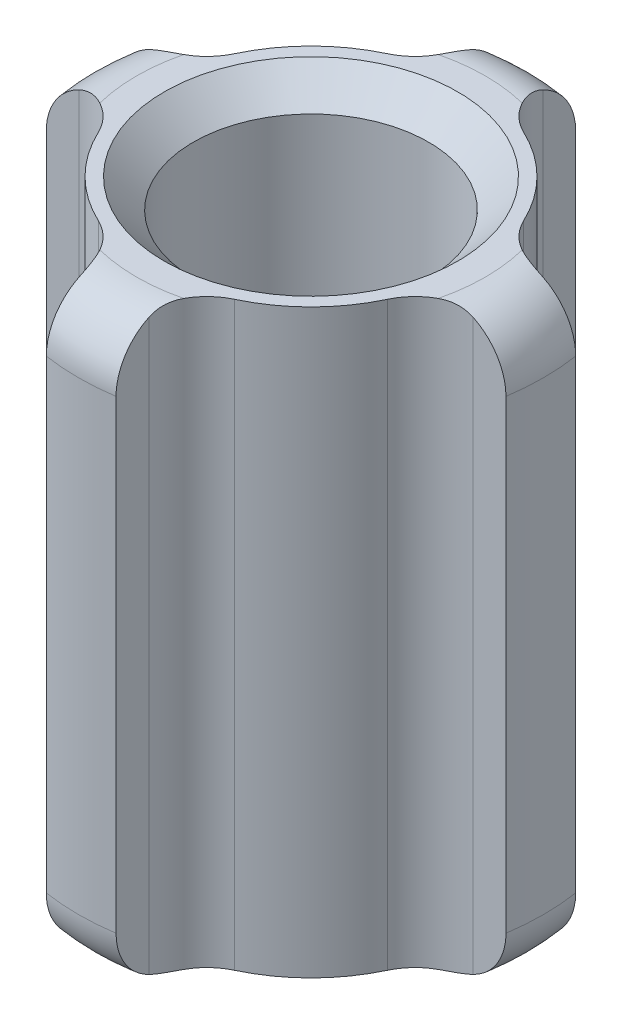
SolidWorks part; units mm, degrees
material "ABS"
ref_plane "Front Plane" through (0, 0, 0) normal (0, 0, 1) x (1, 0, 0)
ref_plane "Top Plane" through (0, 0, 0) normal (0, 1, 0) x (1, 0, 0)
ref_plane "Right Plane" through (0, 0, 0) normal (1, 0, 0) x (0, 0, -1)
sketch "Sketch1" plane through (0, 0, 0) normal (0, 1, 0) x (1, 0, 0)
  line L0 (-0.6, -3.9547) -> (-0.6, -2.6837)
  line L1 (0.6, -3.9547) -> (0.6, -2.6837)
  line L2 (-0.6, 2.6837) -> (-0.6, 3.9547)
  line L3 (0.6, 2.6837) -> (0.6, 3.9547)
  line L4 (-3.9547, 0.6) -> (-2.6837, 0.6)
  line L5 (-3.9547, -0.6) -> (-2.6837, -0.6)
  line L6 (2.6837, -0.6) -> (3.9547, -0.6)
  line L7 (2.6837, 0.6) -> (3.9547, 0.6)
  circle A0 centre (0, 0) radius 2.025
  arc A1 (-0.6, -3.9547) -> (0.6, -3.9547) centre (0, 0) ccw
  arc A2 (-0.6, 2.6837) -> (-2.6837, 0.6) centre (0, 0) ccw
  arc A3 (-3.9547, 0.6) -> (-3.9547, -0.6) centre (0, 0) ccw
  arc A4 (0.6, 3.9547) -> (-0.6, 3.9547) centre (0, 0) ccw
  arc A5 (3.9547, -0.6) -> (3.9547, 0.6) centre (0, 0) ccw
  arc A6 (-2.6837, -0.6) -> (-0.6, -2.6837) centre (0, 0) ccw
  arc A7 (0.6, -2.6837) -> (2.6837, -0.6) centre (0, 0) ccw
  arc A8 (2.6837, 0.6) -> (0.6, 2.6837) centre (0, 0) ccw
  dimension "D1" = 4.05
  dimension "D2" = 8
  dimension "D5" = 5.5
  dimension "D3" = 1.2
  dimension "D4" = 1.2
extrude "Boss-Extrude1" add sketch "Sketch1" along normal blind 10
fillet "Fillet1" radius 1 8 edges at (-4, 10, 0) (-4, 0, 0) (0, 10, 4) (0, 0, 4) (0, 10, -4) (0, 0, -4) (4, 0, 0) (4, 10, 0)
chamfer "Chamfer1" distance 0.5 angle 45 2 edges at (0, 0, 2.025) (0, 10, 2.025)
fillet "Fillet2" radius 1 8 edges at (0.6, 5, -2.6837) (2.6837, 5, -0.6) (2.6837, 5, 0.6) (0.6, 5, 2.6837) (-0.6, 5, 2.6837) (-2.6837, 5, 0.6) (-2.6837, 5, -0.6) (-0.6, 5, -2.6837)
equation "\"D4@Sketch1\"=\"D3@Sketch1\""
